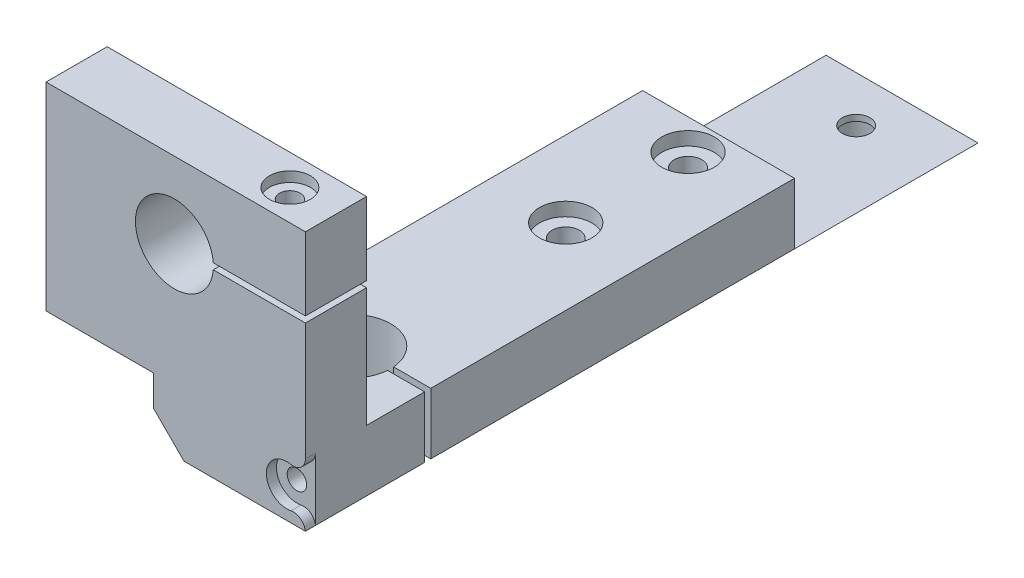
SolidWorks part; units mm, degrees
ref_plane "Front Plane" through (0, 0, 0) normal (0, 0, 1) x (1, 0, 0)
ref_plane "Top Plane" through (0, 0, 0) normal (0, 1, 0) x (1, 0, 0)
ref_plane "Right Plane" through (0, 0, 0) normal (1, 0, 0) x (0, 0, -1)
sketch "Sketch1" plane through (0, 0, 0) normal (0, 1, 0) x (1, 0, 0)
  line L1 (-12.425, 55) -> (12.425, 55)
  line L2 (-12.425, 55) -> (-12.425, -55)
  line L3 (-12.425, -55) -> (12.425, -55)
  line L4 (12.425, 55) -> (12.425, -55)
  line L5 (-12.425, 55) -> (12.425, -55) construction
  line L6 (-12.425, -55) -> (12.425, 55) construction
  point P0 (0, 0)
  dimension "D1" = 24.85
  dimension "D2" = 110
extrude "Boss-Extrude1" add sketch "Sketch1" along normal blind 15
sketch "Sketch2" plane through (0, 15, 0) normal (0, 1, 0) x (1, 0, 0)
  line L0 (12.425, -55) -> (12.425, 55) construction
  line L1 (-12.425, 55) -> (12.425, 55)
  line L2 (-12.425, 55) -> (-12.425, 25)
  line L3 (-12.425, 25) -> (12.425, 25)
  line L4 (12.425, 55) -> (12.425, 25)
  dimension "D1" = 30
extrude "Cut-Extrude1" cut sketch "Sketch2" against normal blind 10
sketch "Sketch3" plane through (0, 15, 0) normal (0, 1, 0) x (1, 0, 0)
  line L0 (12.425, -55) -> (12.425, 25) construction
  line L1 (12.425, -20) -> (2.425, -20)
  line L2 (12.425, -20) -> (12.425, 10)
  line L3 (12.425, 10) -> (2.425, 10)
  line L4 (2.425, -20) -> (2.425, 10)
  line L5 (-12.425, 25) -> (12.425, 25) construction
  dimension "D1" = 30
  dimension "D2" = 10
  dimension "D3" = 15
extrude "Cut-Extrude2" [suppressed] cut sketch "Sketch3" against normal through all
sketch "Sketch4" plane through (-12.425, 0, 0) normal (-1, 0, 0) x (0, 0, 1)
  line L1 (55, 0) -> (20, 0)
  line L2 (55, 0) -> (55, 5)
  line L3 (55, 5) -> (20, 5)
  line L4 (20, 0) -> (20, 5)
  dimension "D1" = 5
  dimension "D2" = 35
extrude "Cut-Extrude3" cut sketch "Sketch4" against normal through all
sketch "Sketch5" plane through (0, 15, 0) normal (0, 1, 0) x (1, 0, 0)
  line L1 (-12.425, -55) -> (-30, -55)
  line L2 (-12.425, -55) -> (-12.425, -45)
  line L3 (-12.425, -45) -> (-30, -45)
  line L4 (-30, -55) -> (-30, -45)
  dimension "D1" = 10
  dimension "D2" = 30
extrude "Boss-Extrude2" add sketch "Sketch5" against normal up to surface (10 mm away) up to face at (0, 5, 37.5)
sketch "Sketch6" plane through (0, 15, 0) normal (0, 1, 0) x (1, 0, 0)
  line L0 (-30, -45) -> (-30, -55) construction
  line L1 (12.425, -55) -> (-30, -55)
  line L2 (12.425, -55) -> (12.425, -45)
  line L3 (12.425, -45) -> (-30, -45)
  line L4 (-30, -55) -> (-30, -45)
  dimension "D1" = 10
extrude "Boss-Extrude3" add sketch "Sketch6" along normal blind 32.42
fillet "Fillet1" [suppressed] radius 10
chamfer "Chamfer2" distance 5 angle 45 2 edges at (12.425, 0, -17.5) (-12.425, 0, -17.5)
sketch "Sketch7" plane through (0, 15, 0) normal (0, 1, 0) x (1, 0, 0)
  circle A0 centre (0, -35) radius 6.375
  dimension "D1" = 12.75
  dimension "D2" = 35
extrude "Cut-Extrude4" cut sketch "Sketch7" against normal through all
sketch "Sketch8" plane through (0, 0, 45) normal (0, 0, -1) x (-1, 0, 0)
  line L0 (-12.425, 5) -> (12.425, 5) construction
  circle A0 centre (9, 35) radius 6.375
  dimension "D1" = 12.75
  dimension "D2" = 30
  dimension "D3" = 9
extrude "Cut-Extrude5" cut sketch "Sketch8" against normal through all
hole_wizard "CBORE for M4 SHCS1" positions "Sketch9" profile "Sketch10" counterbore size "M4" standard "ANSI Metric"
sketch "Sketch9" plane through (0, 0, 0) normal (0, -1, 0) x (-1, 0, 0)
  line L0 (0, 55) -> (0, 47.5) construction
  line L1 (-7.425, 55) -> (7.425, 55) construction
  line L2 (0, 47.5) -> (0, 40) construction
  line L3 (0, 40) -> (0, 32.5) construction
  line L4 (0, 32.5) -> (0, 25) construction
  point P0 (0, 47.5)
  point P2 (0, 32.5)
  dimension "D1" = 30
sketch "Sketch10" plane through (0, 0, -47.5) normal (1, 0, 0) x (0, 0, -1)
  line L0 (0, 0) -> (0, 11.4519)
  line L1 (0, 11.4519) -> (2.25, 10.1)
  line L2 (2.25, 10.1) -> (2.25, 4)
  line L3 (2.25, 4) -> (4, 4)
  line L4 (4, 4) -> (4, 0)
  line L5 (4, 0) -> (0, 0)
  line L10 (0, 11.4519) -> (-2.25, 10.1) construction
  line L11 (0, -6.35) -> (0, 107.95) construction
  dimension "Hole Dia." = 4.5
  dimension "Hole Depth" = 10.1
  dimension "C'Bore Dia." = 8
  dimension "C'Bore Depth" = 4
  dimension "Drill Angle" = 118
hole_wizard "M4x0.7 Tapped Hole1" positions "Sketch13" profile "Sketch14" tap size "M4x0.7" standard "ANSI Metric" end condition through all
sketch "Sketch13" plane through (0, 0, 0) normal (0, -1, 0) x (-1, 0, 0)
  line L0 (-7.425, 55) -> (7.425, 55) construction
  point P0 (0, 20)
  point P2 (0, 0)
  dimension "D1" = 20
  dimension "D2" = 35
sketch "Sketch14" plane through (0, 0, -20) normal (1, 0, 0) x (0, 0, -1)
  line L0 (0, 0) -> (0, 47.42)
  line L1 (0, 47.42) -> (1.65, 47.42)
  line L2 (1.65, 47.42) -> (1.65, 0)
  line L5 (1.65, 0) -> (0, 0)
  line L11 (0, -6.35) -> (0, 107.95) construction
  dimension "Thru Tap Drill Dia." = 3.3
  dimension "Thru Tap Drill Depth" = 47.42
cosmetic thread "Hole Thread1"
cosmetic thread "Hole Thread2"
sketch "Sketch15" plane through (0, 0, 45) normal (0, 0, -1) x (-1, 0, 0)
  line L0 (30, 5) -> (30, 47.42) construction
  line L1 (12.425, 5) -> (30, 5)
  line L2 (12.425, 5) -> (12.425, 15)
  line L3 (12.425, 15) -> (30, 15)
  line L4 (30, 5) -> (30, 15)
extrude "Cut-Extrude6" cut sketch "Sketch15" against normal through all
chamfer "Chamfer6" distance 5 angle 45 1 edges at (-12.425, 5, 37.5)
sketch "Sketch16" plane through (0, 15, 0) normal (0, 1, 0) x (1, 0, 0)
  line L0 (0, -35) -> (12.425, -35) construction
  line L1 (12.425, -45) -> (12.425, 25) construction
  line L3 (4.925, -34.5) -> (19.925, -34.5)
  line L4 (4.925, -34.5) -> (4.925, -35.5)
  line L5 (4.925, -35.5) -> (19.925, -35.5)
  line L6 (19.925, -34.5) -> (19.925, -35.5)
  line L7 (4.925, -34.5) -> (19.925, -35.5) construction
  line L8 (4.925, -35.5) -> (19.925, -34.5) construction
  dimension "D1" = 1
  dimension "D2" = 15
extrude "Cut-Extrude7" cut sketch "Sketch16" against normal through all
sketch "Sketch17" plane through (0, 0, 55) normal (0, 0, 1) x (1, 0, 0)
  line L1 (12.425, 15) -> (6.3554, 15) construction
  line L2 (12.425, 15) -> (12.425, 5) construction
  line L3 (12.425, 5) -> (6.3554, 5) construction
  line L4 (6.3554, 15) -> (6.3554, 5) construction
hole_wizard "CBORE for M3 SBHCS1" positions "3DSketch1" profile "Sketch20" counterbore size "M3" standard "ANSI Metric" end condition up to next
sketch3d "3DSketch1"
  line L0 (12.425, 15, 55) -> (6.3554, 5, 55) construction
  point P0 (9.3902, 10, 55)
sketch "Sketch20" plane through (9.3902, 10, 55) normal (1, 0, 0) x (0, -1, 0)
  line L0 (0, 0) -> (0, 19.5)
  line L1 (0, 19.5) -> (1.6, 19.5)
  line L3 (1.6, 19.5) -> (1.6, 1.65)
  line L4 (1.6, 1.65) -> (3.35, 1.65)
  line L5 (3.35, 1.65) -> (3.35, 0)
  line L7 (3.35, 0) -> (0, 0)
  line L11 (0, -6.35) -> (0, 107.95) construction
  dimension "Thru Hole Dia." = 3.2
  dimension "Thru Hole Depth" = 19.5
  dimension "C'Bore Dia." = 6.7
  dimension "C'Bore Depth" = 1.65
hole_wizard "M3x0.5 Tapped Hole1" positions "Sketch21" profile "Sketch23" tap size "M3x0.5" standard "ANSI Metric"
sketch "Sketch21" plane through (0, 0, 34.5) normal (0, 0, 1) x (1, 0, 0)
  point P0 (9.3902, 10)
sketch "Sketch23" plane through (9.3902, 10, 34.5) normal (1, 0, 0) x (0, -1, 0)
  line L0 (0, 0) -> (0, 8.2511)
  line L1 (0, 8.2511) -> (1.25, 7.5)
  line L2 (1.25, 7.5) -> (1.25, 0)
  line L5 (1.25, 0) -> (0, 0)
  line L10 (0, 8.2511) -> (-1.25, 7.5) construction
  line L11 (0, -6.35) -> (0, 107.95) construction
  dimension "Tap Drill Dia." = 2.5
  dimension "Tap Drill Depth" = 7.5
  dimension "Drill Angle" = 118
cosmetic thread "Hole Thread3"
sketch "Sketch24" plane through (0, 0, 55) normal (0, 0, 1) x (1, 0, 0)
  line L0 (-9, 35) -> (12.425, 35) construction
  line L1 (12.425, 47.42) -> (12.425, 11.4186) construction
  line L3 (-9.575, 35.5) -> (12.425, 35.5)
  line L4 (-9.575, 35.5) -> (-9.575, 34.5)
  line L5 (-9.575, 34.5) -> (12.425, 34.5)
  line L6 (12.425, 35.5) -> (12.425, 34.5)
  line L7 (-9.575, 35.5) -> (12.425, 34.5) construction
  line L8 (-9.575, 34.5) -> (12.425, 35.5) construction
  point P5 (1.425, 35)
  dimension "D1" = 1
  dimension "D2" = 22
extrude "Cut-Extrude8" cut sketch "Sketch24" against normal up to next
sketch "Sketch25" plane through (0, 47.42, 0) normal (0, 1, 0) x (1, 0, 0)
  line L1 (12.425, -45) -> (-2.6446, -45) construction
  line L2 (12.425, -45) -> (12.425, -55) construction
  line L3 (12.425, -55) -> (-2.6446, -55) construction
  line L4 (-2.6446, -45) -> (-2.6446, -55) construction
hole_wizard "CBORE for M3 SBHCS2" positions "Sketch26" profile "Sketch28" counterbore size "M3" standard "ANSI Metric" end condition up to next
sketch "Sketch26" plane through (0, 47.42, 0) normal (0, 1, 0) x (1, 0, 0)
  line L0 (-2.6446, -55) -> (12.425, -45) construction
  point P0 (4.8902, -50)
sketch "Sketch28" plane through (4.8902, 47.42, 50) normal (1, 0, 0) x (0, 0, 1)
  line L0 (0, 0) -> (0, 11.92)
  line L1 (0, 11.92) -> (1.7, 11.92)
  line L3 (1.7, 11.92) -> (1.7, 1.65)
  line L4 (1.7, 1.65) -> (3.35, 1.65)
  line L5 (3.35, 1.65) -> (3.35, 0)
  line L7 (3.35, 0) -> (0, 0)
  line L11 (0, -6.35) -> (0, 107.95) construction
  dimension "Thru Hole Dia." = 3.4
  dimension "Thru Hole Depth" = 11.92
  dimension "C'Bore Dia." = 6.7
  dimension "C'Bore Depth" = 1.65
hole_wizard "M3x0.5 Tapped Hole2" positions "Sketch29" profile "Sketch31" tap size "M3x0.5" standard "ANSI Metric"
sketch "Sketch29" plane through (0, 34.5, 0) normal (0, 1, 0) x (1, 0, 0)
  point P0 (4.8902, -50)
sketch "Sketch31" plane through (4.8902, 34.5, 50) normal (1, 0, 0) x (0, 0, 1)
  line L0 (0, 0) -> (0, 8.2511)
  line L1 (0, 8.2511) -> (1.25, 7.5)
  line L2 (1.25, 7.5) -> (1.25, 0)
  line L5 (1.25, 0) -> (0, 0)
  line L10 (0, 8.2511) -> (-1.25, 7.5) construction
  line L11 (0, -6.35) -> (0, 107.95) construction
  dimension "Tap Drill Dia." = 2.5
  dimension "Tap Drill Depth" = 7.5
  dimension "Drill Angle" = 118
cosmetic thread "Hole Thread4"
hole_wizard "M4x0.7 Tapped Hole2" positions "Sketch32" profile "Sketch34" tap size "M4x0.7" standard "ANSI Metric"
sketch "Sketch32" plane through (-30, 0, 0) normal (-1, 0, 0) x (0, 0, 1)
  line L0 (50, 47.42) -> (50, 35) construction
  line L1 (45, 47.42) -> (55, 47.42) construction
  point P0 (50, 35)
  dimension "D1" = 12.42
sketch "Sketch34" plane through (-30, 35, 50) normal (0, 1, 0) x (0, 0, 1)
  line L0 (0, 0) -> (0, 11.0914)
  line L1 (0, 11.0914) -> (1.65, 10.1)
  line L2 (1.65, 10.1) -> (1.65, 0)
  line L5 (1.65, 0) -> (0, 0)
  line L10 (0, 11.0914) -> (-1.65, 10.1) construction
  line L11 (0, -6.35) -> (0, 107.95) construction
  dimension "Tap Drill Dia." = 3.3
  dimension "Tap Drill Depth" = 10.1
  dimension "Drill Angle" = 118
cosmetic thread "Hole Thread5"
hole_wizard "CBORE for M4 SBHCS1" positions "Sketch35" profile "Sketch36" counterbore size "M4" standard "ANSI Metric" end condition through all
sketch "Sketch35" plane through (0, 15, 0) normal (0, 1, 0) x (1, 0, 0)
  point P0 (0, 20)
  point P3 (0, 0)
sketch "Sketch36" plane through (0, 15, -20) normal (1, 0, 0) x (0, 0, 1)
  line L0 (0, 0) -> (0, 15)
  line L1 (0, 15) -> (2.25, 15)
  line L3 (2.25, 15) -> (2.25, 2.2)
  line L4 (2.25, 2.2) -> (4.3, 2.2)
  line L5 (4.3, 2.2) -> (4.3, 0)
  line L7 (4.3, 0) -> (0, 0)
  line L11 (0, -6.35) -> (0, 107.95) construction
  dimension "Thru Hole Dia." = 4.5
  dimension "Thru Hole Depth" = 15
  dimension "C'Bore Dia." = 8.6
  dimension "C'Bore Depth" = 2.2
fillet "Fillet2" radius 2 2 edges at (12.425, 8.5814, 54.175) (12.425, 11.4186, 54.175)
